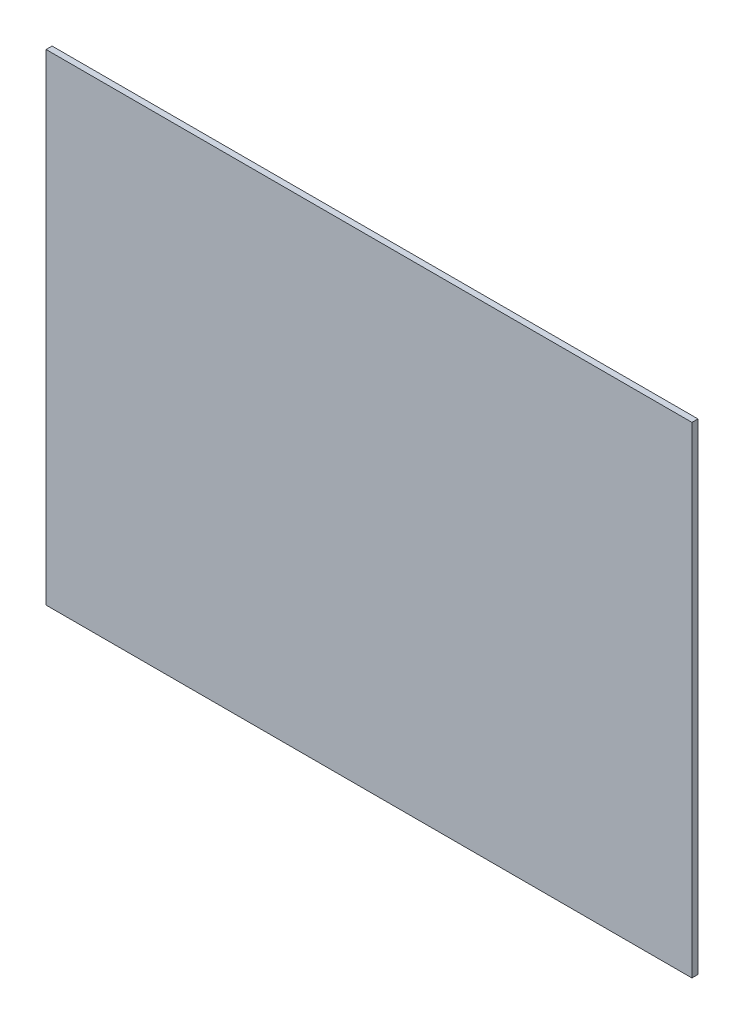
SolidWorks part; units mm, degrees
material "Acrylic (Medium-high impact)"
ref_plane "Front Plane" through (0, 0, 0) normal (0, 0, 1) x (1, 0, 0)
ref_plane "Top Plane" through (0, 0, 0) normal (0, 1, 0) x (1, 0, 0)
ref_plane "Right Plane" through (0, 0, 0) normal (1, 0, 0) x (0, 0, -1)
sketch "Sketch2" plane through (0, 0, 0) normal (0, 0, 1) x (1, 0, 0)
  line L1 (0, 0) -> (254, 0)
  line L2 (0, 0) -> (0, 189.23)
  line L3 (0, 189.23) -> (254, 189.23)
  line L4 (254, 0) -> (254, 189.23)
extrude "Boss-Extrude1" add sketch "Sketch2" along normal blind 2.3622
